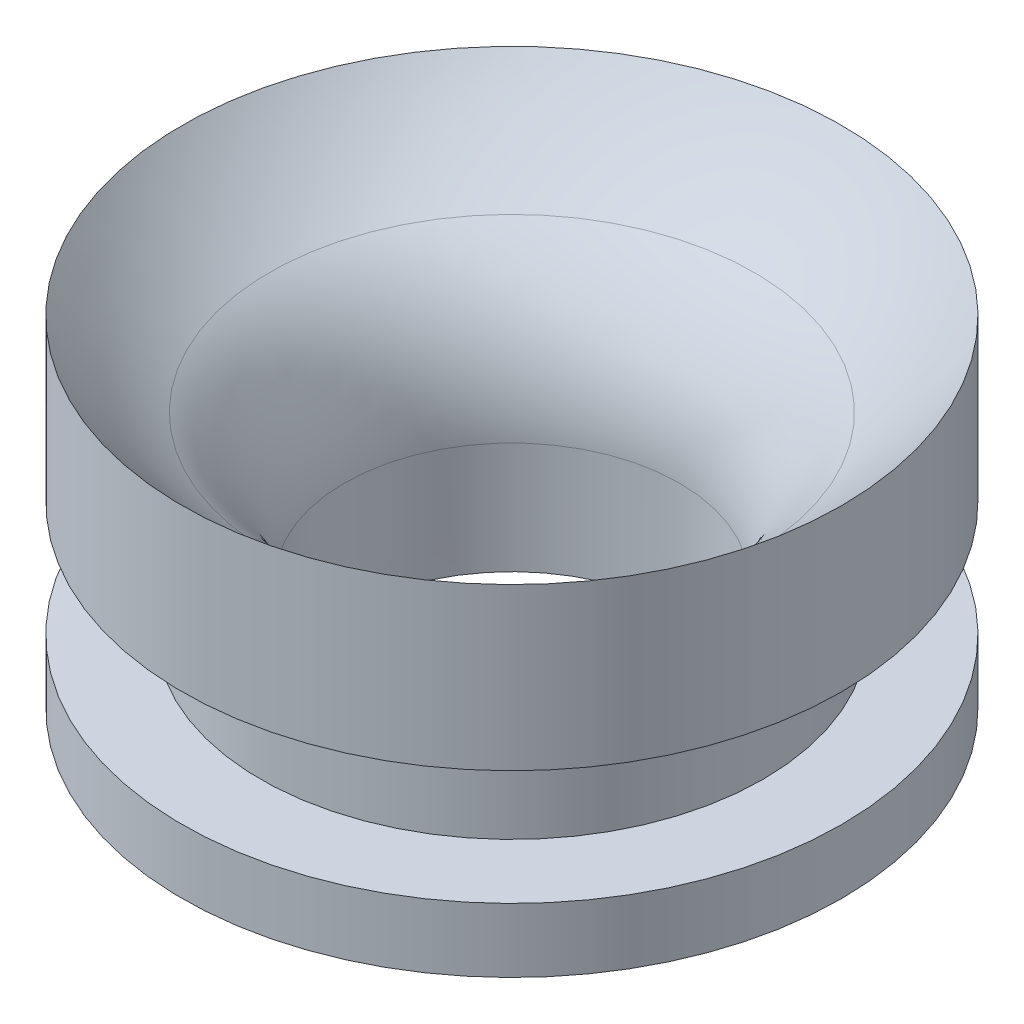
SolidWorks part; units mm, degrees
ref_plane "Front Plane" through (0, 0, 0) normal (0, 0, 1) x (1, 0, 0)
ref_plane "Top Plane" through (0, 0, 0) normal (0, 1, 0) x (1, 0, 0)
ref_plane "Right Plane" through (0, 0, 0) normal (1, 0, 0) x (0, 0, -1)
sketch "Sketch3" plane through (0, 0, 0) normal (0, 0, 1) x (1, 0, 0)
  line L0 (0, 0) -> (9.398, 0)
  line L1 (9.398, 0) -> (9.398, 1.8288)
  line L2 (9.398, 1.8288) -> (7.1628, 1.8288)
  line L3 (7.1628, 1.8288) -> (7.1628, 5.1054)
  line L4 (7.1628, 5.1054) -> (9.398, 5.1054)
  line L5 (9.398, 5.1054) -> (9.398, 9.7028)
  line L6 (0, 0) -> (0, 5.1054)
  line L8 (7.1628, 5.1054) -> (0, 5.1054)
  arc A0 (0, 5.1054) -> (9.398, 9.7028) centre (0, 17.0098) ccw
  dimension "D1" = 1.8288
  dimension "D2" = 3.2766
  dimension "D3" = 4.5974
  dimension "D4" = 2.2352
  dimension "D5" = 2.2352
revolve "Revolve3" add sketch "Sketch3" angle 360 about L6 region at (4.0539, 2.388, 0) region at (7.1488, 6.4228, 0)
sketch "Sketch4" plane through (0, 0, 0) normal (0, -1, 0) x (1, 0, 0)
  circle A0 centre (0, 0) radius 4.7752
extrude "Cut-Extrude1" cut sketch "Sketch4" against normal blind 12.446
fillet "Fillet2" radius 5.08 1 edges at (-4.7752, 6.1051, 0)
ref_axis "Axis1" through (0, -0.4851, 0) along (0, 1, 0)
